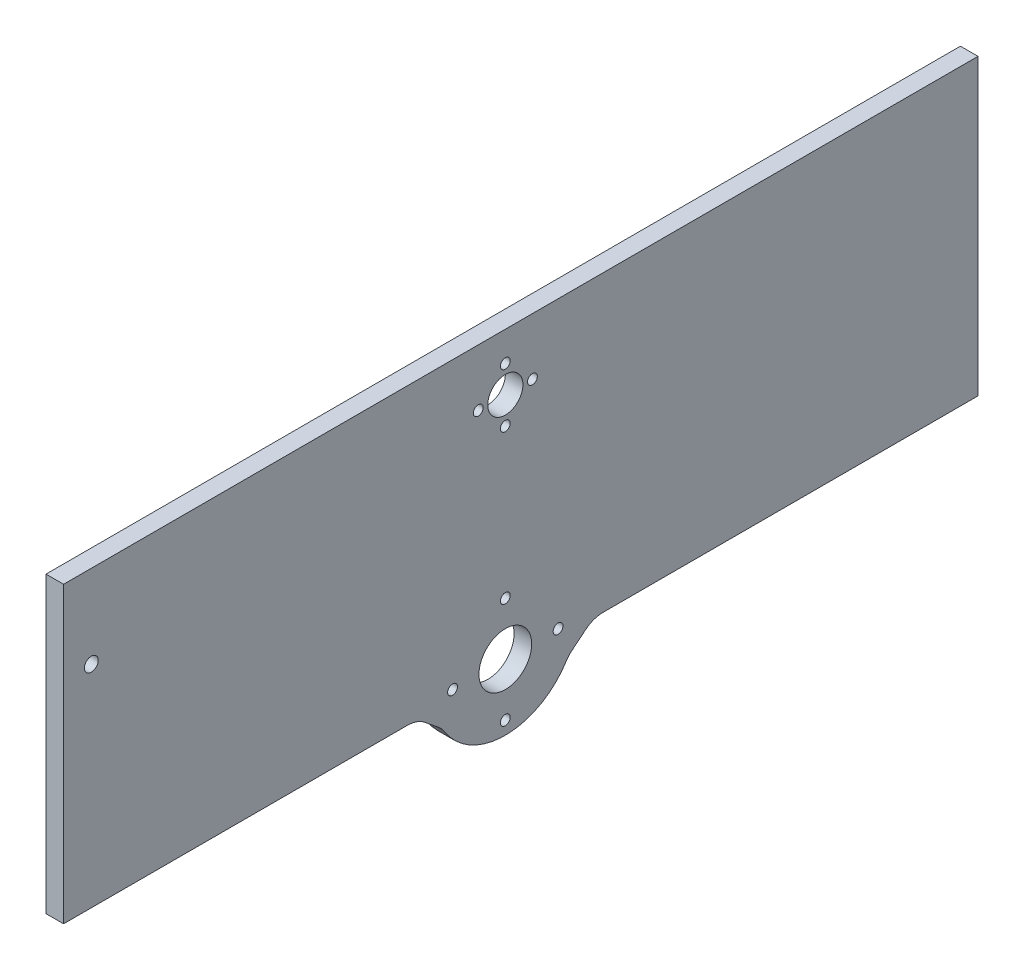
SolidWorks part; units mm, degrees
ref_plane "Front Plane" through (0, 0, 0) normal (0, 0, 1) x (1, 0, 0)
ref_plane "Top Plane" through (0, 0, 0) normal (0, 1, 0) x (1, 0, 0)
ref_plane "Right Plane" through (0, 0, 0) normal (1, 0, 0) x (0, 0, -1)
sketch "Sketch1" plane through (0, 0, 0) normal (1, 0, 0) x (0, 0, -1)
  line L1 (0, 0) -> (330.2, 0)
  line L2 (0, 0) -> (0, 127)
  line L3 (0, 127) -> (330.2, 127)
  line L4 (330.2, 0) -> (330.2, 127)
  dimension "D1" = 330.2
  dimension "D2" = 127
extrude "Main Plate Size" add sketch "Sketch1" along normal blind 6.35
sketch "Sketch2" plane through (6.35, 0, 0) normal (1, 0, 0) x (0, 0, -1)
  line L0 (178.562, 23.8252) -> (159.512, 42.8752) construction
  line L1 (0, 0) -> (330.2, 0) construction
  line L2 (178.562, 23.8252) -> (159.512, 4.7752) construction
  line L3 (159.512, 42.8752) -> (140.462, 23.8252) construction
  line L4 (159.512, 4.7752) -> (140.462, 23.8252) construction
  line L5 (178.562, 23.8252) -> (140.462, 23.8252) construction
  line L6 (159.512, 42.8752) -> (159.512, 4.7752) construction
  line L7 (0, 127) -> (0, 0) construction
  line L9 (0, 20.8026) -> (134.112, 20.8026)
  line L10 (184.912, 20.8026) -> (330.2, 20.8026)
  line L11 (330.2, 0) -> (330.2, 127) construction
  line L12 (0, 20.8026) -> (0, 0)
  line L13 (330.2, 0) -> (330.2, 20.8026)
  line L15 (0, 0) -> (177.8, 0)
  line L16 (177.8, 0) -> (330.2, 0)
  circle A0 centre (159.512, 23.8252) radius 9.525
  circle A1 centre (159.512, 42.8752) radius 1.778
  circle A2 centre (178.562, 23.8252) radius 1.778
  circle A3 centre (159.512, 4.7752) radius 1.778
  circle A4 centre (140.462, 23.8252) radius 1.778
  arc A5 (134.112, 20.8026) -> (184.912, 20.8026) centre (159.512, 25.908) ccw
  point P24 (134.112, 20.8026)
  line M11 (0, 127) -> (0, 0)
  line M12 (0, 0) -> (330.2, 0)
  line M13 (330.2, 0) -> (330.2, 127)
  dimension "D1" = 19.05
  dimension "D2" = 3.556
  dimension "D6" = 25.908
  dimension "D3" = 38.1
  dimension "D4" = 159.512
  dimension "D5" = 5.1054
  dimension "D7" = 2.0828
extrude "Bottom Shaft Mounting Holes" cut sketch "Sketch2" against normal through all contours A5 L9 M11 M12 | A5 L10 M12 M13 | A0 | A3 | A2 | A1 | A4 region at (6.35, 10.1874, -254.2605) region at (6.35, 10.1704, -70.3601) region at (6.35, 23.8252, -159.512) region at (6.35, 42.8752, -159.512) region at (6.35, 23.8252, -178.562) region at (6.35, 4.7752, -159.512) region at (6.35, 23.8252, -140.462)
sketch "Sketch3" plane through (6.35, 0, 0) normal (1, 0, 0) x (0, 0, -1)
  line L0 (159.512, 23.8252) -> (159.512, 106.5022) construction
  line L2 (159.512, 116.2812) -> (149.733, 106.5022) construction
  line L3 (149.733, 106.5022) -> (159.512, 96.7232) construction
  line L4 (159.512, 96.7232) -> (169.291, 106.5022) construction
  line L5 (169.291, 106.5022) -> (159.512, 116.2812) construction
  circle A0 centre (159.512, 106.5022) radius 6.35
  circle A1 centre (159.512, 106.5022) radius 9.779 construction
  circle A2 centre (149.733, 106.5022) radius 1.778
  circle A3 centre (159.512, 116.2812) radius 1.778
  circle A4 centre (169.291, 106.5022) radius 1.778
  circle A5 centre (159.512, 96.7232) radius 1.778
  dimension "D2" = 12.7
  dimension "D3" = 19.558
  dimension "D4" = 3.556
  dimension "D1" = 82.677
extrude "Top Battery Box Mounting Holes" cut sketch "Sketch3" against normal through all
chamfer "This is to match the idiotic Design of B Box" distance 6.35 distance2 6.35 2 edges at (3.175, 20.8026, -184.912) (3.175, 20.8026, -134.112)
fillet "This is to match the idiotic Design of B Box2" radius 10 4 edges at (3.175, 20.8026, -191.262) (3.175, 13.366, -182.1818) (3.175, 13.366, -136.8422) (3.175, 20.8026, -127.762)
sketch "Sketch4" plane through (6.35, 0, 0) normal (1, 0, 0) x (0, 0, -1)
  line L0 (0, 127) -> (0, 20.8026) construction
  line L1 (20, 87.0026) -> (0, 87.0026) construction
  line L2 (20, 87.0026) -> (20, 107.0026) construction
  line L3 (20, 107.0026) -> (0, 107.0026) construction
  line L4 (0, 87.0026) -> (0, 107.0026) construction
  line L5 (20, 87.0026) -> (0, 107.0026) construction
  line L6 (20, 107.0026) -> (0, 87.0026) construction
  line L7 (0, 20.8026) -> (124.1896, 20.8026) construction
  circle A0 centre (10, 97.0026) radius 2.5
  point P0 (10, 97.0026)
  dimension "D2" = 5
  dimension "D1" = 20
  dimension "D3" = 76.2
extrude "20mm Extrusion Mount" cut sketch "Sketch4" against normal through all
sketch "Sketch5" plane through (6.35, 0, 0) normal (1, 0, 0) x (0, 0, -1)
  line L0 (20, 87.0026) -> (0, 87.0026) construction
  line L1 (20, 87.0026) -> (0, 87.0026)
  line L2 (20, 87.0026) -> (20, 20.8026)
  line L3 (0, 20.8026) -> (124.1896, 20.8026) construction
  line L4 (0, 87.0026) -> (0, 20.8026)
  line L5 (0, 20.8026) -> (20, 20.8026)
